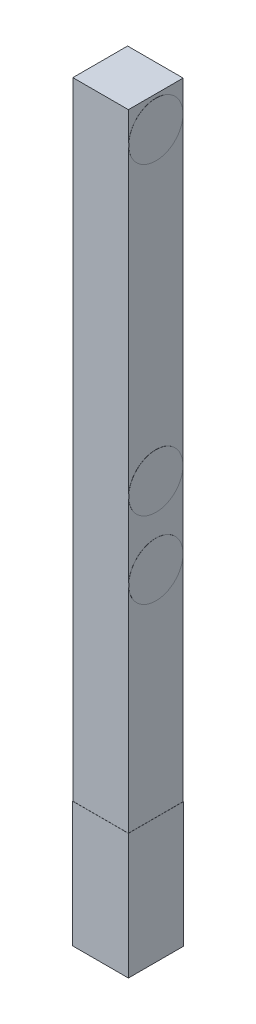
SolidWorks part; units mm, degrees
material "Alloy Steel"
ref_plane "Front Plane" through (0, 0, 0) normal (0, 0, 1) x (1, 0, 0)
ref_plane "Top Plane" through (0, 0, 0) normal (0, 1, 0) x (1, 0, 0)
ref_plane "Right Plane" through (0, 0, 0) normal (1, 0, 0) x (0, 0, -1)
sketch "Sketch1" plane through (0, 0, 0) normal (0, 1, 0) x (1, 0, 0)
  line L1 (-22.51, -22.1884) -> (22.51, -22.1884)
  line L2 (-22.51, -22.1884) -> (-22.51, 22.1884)
  line L3 (-22.51, 22.1884) -> (22.51, 22.1884)
  line L4 (22.51, -22.1884) -> (22.51, 22.1884)
  line L5 (-22.51, -22.1884) -> (22.51, 22.1884) construction
  line L6 (-22.51, 22.1884) -> (22.51, -22.1884) construction
  point P0 (0, 0)
  dimension "D1" = 45.02
extrude "Boss-Extrude1" add sketch "Sketch1" along normal blind 609.6
sketch "Sketch2" plane through (22.51, 0, 0) normal (1, 0, 0) x (0, 0, -1)
  line L0 (-22.1884, 0) -> (22.1884, 0) construction
  line L3 (22.1884, 609.6) -> (22.1884, 0) construction
  line L4 (-22.1884, 609.6) -> (22.1884, 609.6) construction
  circle A0 centre (0, 275.7) radius 22
  circle A1 centre (0, 337.8) radius 22
  circle A2 centre (0, 584.6) radius 22
  point P0 (0, 275.7)
  dimension "D3" = 44
  dimension "D4" = 44
  dimension "D5" = 44
  dimension "D6" = 25
  dimension "D7" = 62.1
  dimension "D1" = 275.7
  dimension "D2" = 22.1884
extrude "Boss-Extrude2" add sketch "Sketch2" along normal blind 0.1
sketch "Sketch3" plane through (22.51, 0, 0) normal (1, 0, 0) x (0, 0, -1)
  line L0 (-22.1884, 0) -> (22.1884, 0) construction
  line L1 (-22.1884, 0) -> (22.1884, 0)
  line L2 (-22.1884, 0) -> (-22.1884, 101.6)
  line L3 (-22.1884, 101.6) -> (22.1884, 101.6)
  line L4 (22.1884, 0) -> (22.1884, 101.6)
  line L5 (22.1884, 609.6) -> (22.1884, 0) construction
  dimension "D1" = 101.6
extrude "Boss-Extrude3" add sketch "Sketch3" along normal blind 0.1
sketch "Sketch4" plane through (0, 0, -22.1884) normal (0, 0, -1) x (-1, 0, 0)
  line L0 (22.51, 609.6) -> (22.51, 0) construction
  line L1 (-22.61, 0) -> (22.51, 0)
  line L2 (-22.61, 0) -> (-22.61, 101.6)
  line L3 (-22.61, 101.6) -> (22.51, 101.6)
  line L4 (22.51, 0) -> (22.51, 101.6)
  dimension "D1" = 101.6
extrude "Boss-Extrude4" add sketch "Sketch4" along normal blind 0.1
sketch "Sketch5" plane through (-22.51, 0, 0) normal (-1, 0, 0) x (0, 0, 1)
  line L0 (22.1884, 609.6) -> (22.1884, 0) construction
  line L1 (-22.2884, 0) -> (22.1884, 0)
  line L2 (-22.2884, 0) -> (-22.2884, 101.6)
  line L3 (-22.2884, 101.6) -> (22.1884, 101.6)
  line L4 (22.1884, 0) -> (22.1884, 101.6)
  dimension "D1" = 101.6
extrude "Boss-Extrude5" add sketch "Sketch5" along normal blind 0.1
sketch "Sketch6" plane through (0, 0, 22.1884) normal (0, 0, 1) x (1, 0, 0)
  line L0 (22.51, 609.6) -> (22.51, 101.6) construction
  line L1 (-22.61, 0) -> (22.51, 0)
  line L2 (-22.61, 0) -> (-22.61, 101.6)
  line L3 (-22.61, 101.6) -> (22.51, 101.6)
  line L4 (22.51, 0) -> (22.51, 101.6)
  dimension "D1" = 101.6
extrude "Boss-Extrude6" add sketch "Sketch6" along normal blind 0.1
